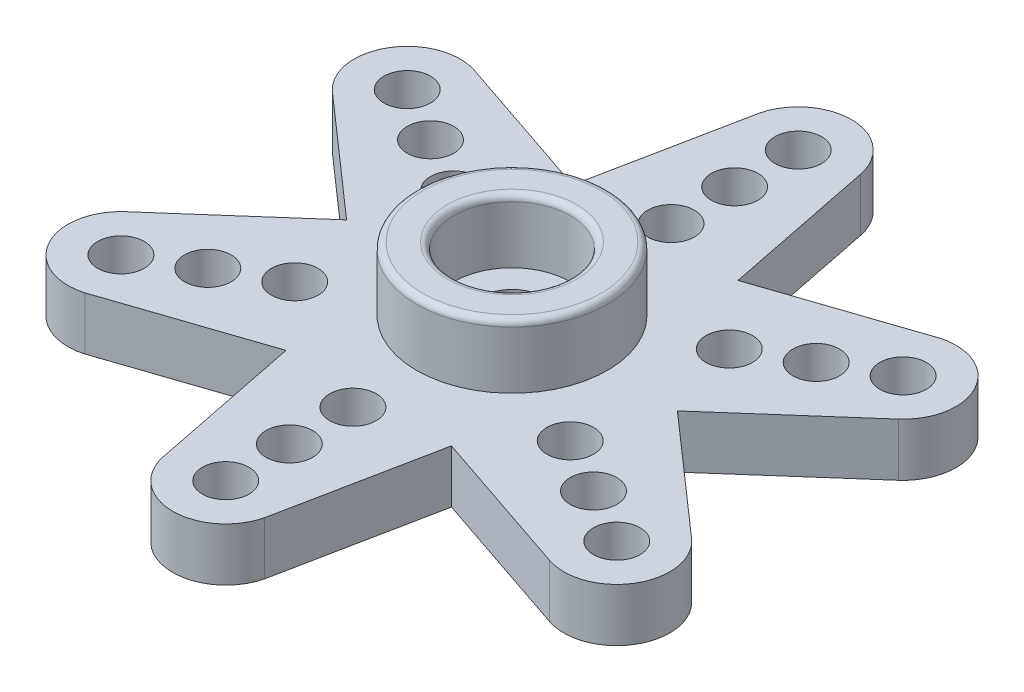
SolidWorks part; units mm, degrees
ref_plane "Alzado" through (0, 0, 0) normal (0, 0, 1) x (1, 0, 0)
ref_plane "Planta" through (0, 0, 0) normal (0, 1, 0) x (1, 0, 0)
ref_plane "Vista lateral" through (0, 0, 0) normal (1, 0, 0) x (0, 0, -1)
sketch "Croquis1" plane through (0, 0, 0) normal (0, 1, 0) x (1, 0, 0)
  line L0 (3.9, -6.755) -> (-3.9, -6.755) construction
  line L1 (0, 0) -> (0, -16) construction
  line L2 (-3.9, -6.755) -> (-10.9949, -9.151)
  line L3 (-13.342, -4.8725) -> (-7.8, 0)
  line L4 (-7.8, 0) -> (-13.4225, 4.9463)
  line L5 (-10.8907, 9.1183) -> (-3.9, 6.755)
  line L6 (-3.9, 6.755) -> (-2.4276, 14.0973)
  line L7 (2.4514, 13.9908) -> (3.9, 6.755)
  line L8 (3.9, 6.755) -> (10.9949, 9.151)
  line L9 (13.342, 4.8725) -> (7.8, 0)
  line L10 (3.9, -6.755) -> (2.4276, -14.0973)
  line L11 (7.8, 0) -> (13.4225, -4.9463)
  line L12 (-2.4514, -13.9908) -> (-3.9, -6.755)
  line L13 (10.8907, -9.1183) -> (3.9, -6.755)
  arc A0 (-13.342, -4.8725) -> (-10.9949, -9.151) centre (-11.6913, -6.75) ccw
  arc A1 (-10.8907, 9.1183) -> (-13.4225, 4.9463) centre (-11.6913, 6.75) ccw
  arc A2 (2.4514, 13.9908) -> (-2.4276, 14.0973) centre (0, 13.5) ccw
  arc A3 (13.342, 4.8725) -> (10.9949, 9.151) centre (11.6913, 6.75) ccw
  arc A4 (-2.4514, -13.9908) -> (2.4276, -14.0973) centre (0, -13.5) ccw
  arc A5 (10.8907, -9.1183) -> (13.4225, -4.9463) centre (11.6913, -6.75) ccw
  circle A6 centre (0, 0) radius 16 construction
  circle A8 centre (0, 0) radius 7.8 construction
  point P35 (0, 0)
  point P37 (0, 0)
  dimension "D1" = 32
  dimension "D5" = 5
  dimension "D2" = 15.6
extrude "Saliente-Extruir1" add sketch "Croquis1" along normal blind 2.5
sketch "Croquis2" plane through (0, 2.5, 0) normal (0, 1, 0) x (1, 0, 0)
  circle A0 centre (0, 0) radius 4.5
  circle A1 centre (0, 0) radius 2.75
  dimension "D1" = 9
  dimension "D2" = 5.5
extrude "Saliente-Extruir2" add sketch "Croquis2" along normal blind 3
sketch "Croquis3" plane through (0, 0, 0) normal (0, -1, 0) x (1, 0, 0)
  circle A0 centre (0, 0) radius 1.5
  dimension "D1" = 3
extrude "Cortar-Extruir1" cut sketch "Croquis3" against normal up to next
sketch "Croquis4" plane through (0, 0, 0) normal (0, -1, 0) x (1, 0, 0)
  circle A0 centre (0, 0) radius 2.8
  dimension "D1" = 5.6
extrude "Cortar-Extruir2" cut sketch "Croquis4" against normal offset from surface (1 mm away) 1.5 up to face at (0, 2.5, 1.5)
sketch "Croquis5" plane through (0, 0, 0) normal (0, -1, 0) x (1, 0, 0)
  circle A0 centre (0, 0) radius 4.5
  circle A1 centre (0, 0) radius 3.5
  dimension "D1" = 9
  dimension "D2" = 7
extrude "Cortar-Extruir3" cut sketch "Croquis5" against normal blind 0.5
fillet "Redondeo1" radius 0.3 5 edges at (0, 0, -4.5) (0, 0, -2.8) (0, 0, -3.5) (0, 5.5, 2.75) (0, 5.5, 4.5)
sketch "Croquis6" plane through (0, 0, 0) normal (0, -1, 0) x (1, 0, 0)
  line L0 (0, 0) -> (0, -16.5) construction
  circle A0 centre (0, 0) radius 10.5 construction
  circle A1 centre (0, 0) radius 13.5 construction
  circle A3 centre (0, 0) radius 7.5 construction
  circle A5 centre (0, -13.5) radius 1.1
  circle A6 centre (0, -10.5) radius 1.1
  circle A7 centre (0, -7.5) radius 1.1
  dimension "D2" = 27
  dimension "D3" = 21
  dimension "D4" = 15
extrude "Cortar-Extruir4" cut sketch "Croquis6" against normal up to next
pattern_circular "MatrizC1" count 6 over 360 about axis through (0, 1, 0) along (0, -1, 0) of "Cortar-Extruir4"
